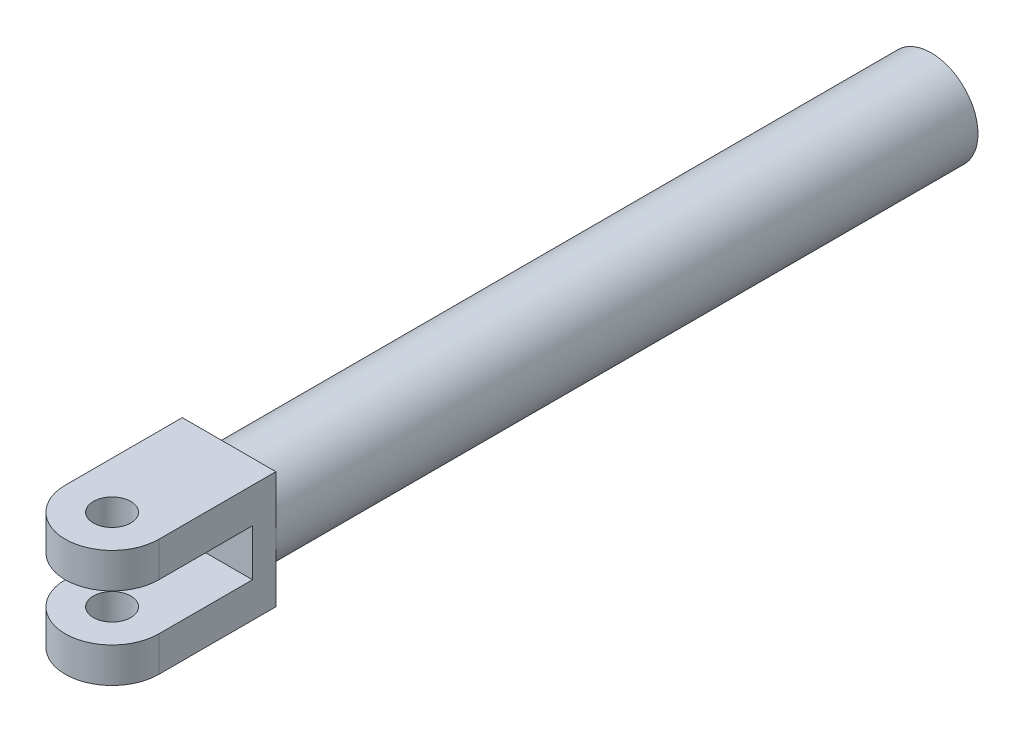
SolidWorks part; units mm, degrees
ref_plane "前视基准面" through (0, 0, 0) normal (0, 0, 1) x (1, 0, 0)
ref_plane "上视基准面" through (0, 0, 0) normal (0, 1, 0) x (1, 0, 0)
ref_plane "右视基准面" through (0, 0, 0) normal (1, 0, 0) x (0, 0, -1)
sketch "草图2" plane through (0, 0, 0) normal (0, 0, 1) x (1, 0, 0)
  circle A0 centre (0, 0) radius 10
  circle A1 centre (0, 0) radius 10 construction
extrude "凸台-拉伸1" add sketch "草图2" along normal blind 150
sketch "草图3" plane through (0, 0, 150) normal (0, 0, 1) x (1, 0, 0)
  line L1 (-10, 12.5) -> (10, 12.5)
  line L2 (-10, 12.5) -> (-10, -12.5)
  line L3 (-10, -12.5) -> (10, -12.5)
  line L4 (10, 12.5) -> (10, -12.5)
  line L5 (0, -12.5) -> (0, 12.5) construction
  line L6 (-10, 0) -> (10, 0) construction
  point P0 (0, 0)
  dimension "D1" = 25
  dimension "D2" = 20
extrude "凸台-拉伸2" add sketch "草图3" along normal blind 35
sketch "草图4" plane through (-10, 0, 0) normal (-1, 0, 0) x (0, 0, 1)
  line L0 (185, 12.5) -> (185, -12.5) construction
  line L1 (155, 5) -> (215, 5)
  line L2 (155, 5) -> (155, -5)
  line L3 (155, -5) -> (215, -5)
  line L4 (215, 5) -> (215, -5)
  line L5 (185, -5) -> (185, 5) construction
  line L6 (155, 0) -> (215, 0) construction
  line L7 (150, 12.5) -> (150, 0) construction
  point P0 (185, 0)
  dimension "D1" = 10
  dimension "D2" = 5
extrude "切除-拉伸1" cut sketch "草图4" against normal blind 50
sketch "草图5" plane through (0, -12.5, 0) normal (0, -1, 0) x (1, 0, 0)
  line L0 (-10, 150) -> (10, 150) construction
  line L1 (-10, 185) -> (10, 185) construction
  line L2 (0, 185) -> (0, 189.4018) construction
  circle A0 centre (0, 175) radius 4
  dimension "D2" = 8
  dimension "D1" = 25
extrude "切除-拉伸2" cut sketch "草图5" against normal blind 50
fillet "圆角3" 2 edges at (10, -8.75, 185) (-10, -8.75, 185) type full round first side face at (10, 0, 166.6667) second side face at (-10, 0, 166.6667) middle face at (0, -8.75, 185)
fillet "圆角4" 2 edges at (-10, 8.75, 185) (10, 8.75, 185) type full round first side face at (-10, 0, 164.4444) second side face at (10, 0, 164.4444) middle face at (0, 8.75, 185)
